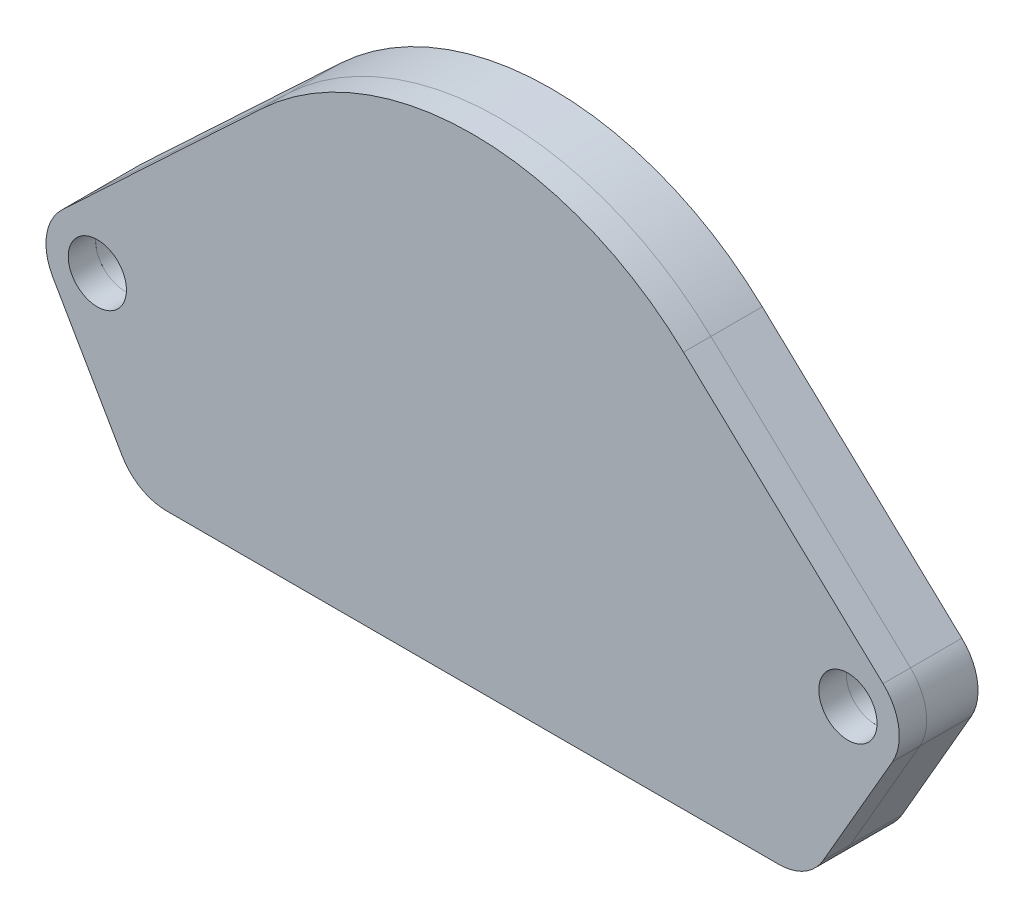
SolidWorks part; units mm, degrees
ref_plane "Front Plane" through (0, 0, 0) normal (0, 0, 1) x (1, 0, 0)
ref_plane "Top Plane" through (0, 0, 0) normal (0, 1, 0) x (1, 0, 0)
ref_plane "Right Plane" through (0, 0, 0) normal (1, 0, 0) x (0, 0, -1)
sketch "Sketch1" plane through (0, 0, 0) normal (0, 0, 1) x (1, 0, 0)
  line L0 (-12.3175, 13.1255) -> (-23.9729, 2.1876)
  line L1 (12.3175, 13.1255) -> (23.9729, 2.1876)
  line L2 (-21.92, 0) -> (21.92, 0) construction
  line L3 (-24.5181, -1.5) -> (-19.6106, -10)
  line L4 (-19.6106, -10) -> (19.6106, -10)
  line L5 (0, -10) -> (0, 0) construction
  line L6 (24.5181, -1.5) -> (19.6106, -10)
  arc A1 (-23.9729, 2.1876) -> (-24.5181, -1.5) centre (-21.92, 0) ccw
  arc A2 (24.5181, -1.5) -> (23.9729, 2.1876) centre (21.92, 0) ccw
  circle A3 centre (-21.92, 0) radius 1.7
  circle A4 centre (21.92, 0) radius 1.7
  arc A5 (12.3175, 13.1255) -> (-12.3175, 13.1255) centre (0, 0) ccw
  point P1 (0, 0)
  point P13 (-21.269, -9.3097)
  point P16 (0, 0)
  point P18 (-24.3403, -1.7726)
  point P19 (-17.123, -9.273)
  dimension "D1" = 43.84
  dimension "D2" = 18
  dimension "D3" = 6
  dimension "D5" = 3.4
  dimension "D4" = 10
  dimension "D6" = 60
extrude "Boss-Extrude1" add sketch "Sketch1" along normal blind 1.6
fillet "Fillet3" radius 3 2 edges at (19.6106, -10, 0.8) (-19.6106, -10, 0.8)
sketch "Sketch2" plane through (0, 0, 0) normal (0, 0, -1) x (-1, 0, 0)
  line L7 (-17.72, 0) -> (-17.72, -8)
  line L8 (17.72, 0) -> (17.72, -8)
  line L9 (-16.2662, 6.6772) -> (-10, 0) construction
  line L10 (-10, 0) -> (-10, -8) construction
  line L11 (-17.3599, 5.6507) -> (-11.5, -0.5936)
  line L12 (-11.5, -0.5936) -> (-11.5, -8)
  line L13 (-15.1724, 7.7036) -> (-8.5, 0.5936)
  line L15 (-17.8785, -8) -> (17.8785, -8)
  line L17 (18.7446, -7.5) -> (22.786, -0.5)
  line L18 (22.6043, 0.7292) -> (10.9489, 11.6671)
  line L19 (-10.9489, 11.6671) -> (-22.6043, 0.7292)
  line L20 (-22.786, -0.5) -> (-18.7446, -7.5)
  line L22 (-17.8785, -8) -> (17.8785, -8)
  line L24 (18.7446, -7.5) -> (22.786, -0.5)
  line L25 (22.6043, 0.7292) -> (10.9489, 11.6671)
  line L26 (-10.9489, 11.6671) -> (-22.6043, 0.7292)
  line L29 (-17.8785, -10) -> (17.8785, -10)
  line L31 (20.4766, -8.5) -> (24.5181, -1.5)
  line L32 (23.9729, 2.1876) -> (12.3175, 13.1255)
  line L33 (-12.3175, 13.1255) -> (-23.9729, 2.1876)
  line L34 (-24.5181, -1.5) -> (-20.4766, -8.5)
  line L36 (-17.8785, -10) -> (17.8785, -10)
  line L38 (20.4766, -8.5) -> (24.5181, -1.5)
  line L39 (23.9729, 2.1876) -> (12.3175, 13.1255)
  line L40 (-12.3175, 13.1255) -> (-23.9729, 2.1876)
  line L42 (-8.5, 0.5936) -> (-8.5, -8)
  line L43 (0, 0) -> (0, -8) construction
  line L44 (8.5, 0.5936) -> (8.5, -8)
  line L45 (10, 0) -> (10, -8) construction
  line L46 (11.5, -0.5936) -> (11.5, -8)
  line L47 (17.3599, 5.6507) -> (11.5, -0.5936)
  line L48 (16.2662, 6.6772) -> (10, 0) construction
  line L49 (15.1724, 7.7036) -> (8.5, 0.5936)
  line L51 (-22.786, -0.5) -> (-18.7446, -7.5)
  line L53 (-24.5181, -1.5) -> (-20.4766, -8.5)
  arc A14 (22.786, -0.5) -> (22.6043, 0.7292) centre (21.92, 0) ccw
  arc A15 (10.9489, 11.6671) -> (-10.9489, 11.6671) centre (0, 0) ccw
  arc A16 (-22.6043, 0.7292) -> (-22.786, -0.5) centre (-21.92, 0) ccw
  arc A17 (22.786, -0.5) -> (22.6043, 0.7292) centre (21.92, 0) ccw
  arc A18 (10.9489, 11.6671) -> (-10.9489, 11.6671) centre (0, 0) ccw
  circle A20 centre (-21.92, 0) radius 4.2
  circle A21 centre (-21.92, 0) radius 4.2
  circle A23 centre (21.92, 0) radius 4.2
  circle A24 centre (21.92, 0) radius 4.2
  arc A27 (-22.6043, 0.7292) -> (-22.786, -0.5) centre (-21.92, 0) ccw
  arc A31 (-18.7446, -7.5) -> (-17.8785, -8) centre (-17.8785, -7) ccw
  arc A33 (-18.7446, -7.5) -> (-17.8785, -8) centre (-17.8785, -7) ccw
  arc A34 (24.5181, -1.5) -> (23.9729, 2.1876) centre (21.92, 0) ccw
  arc A35 (12.3175, 13.1255) -> (-12.3175, 13.1255) centre (0, 0) ccw
  arc A36 (-23.9729, 2.1876) -> (-24.5181, -1.5) centre (-21.92, 0) ccw
  arc A41 (24.5181, -1.5) -> (23.9729, 2.1876) centre (21.92, 0) ccw
  arc A42 (12.3175, 13.1255) -> (-12.3175, 13.1255) centre (0, 0) ccw
  arc A43 (-23.9729, 2.1876) -> (-24.5181, -1.5) centre (-21.92, 0) ccw
  arc A45 (17.8785, -8) -> (18.7446, -7.5) centre (17.8785, -7) ccw
  arc A49 (17.8785, -8) -> (18.7446, -7.5) centre (17.8785, -7) ccw
  arc A53 (-20.4766, -8.5) -> (-17.8785, -10) centre (-17.8785, -7) ccw
  arc A55 (-20.4766, -8.5) -> (-17.8785, -10) centre (-17.8785, -7) ccw
  arc A56 (17.8785, -10) -> (20.4766, -8.5) centre (17.8785, -7) ccw
  arc A57 (17.8785, -10) -> (20.4766, -8.5) centre (17.8785, -7) ccw
  line M29 (-17.8785, -10) -> (17.8785, -10)
  line M33 (20.4766, -8.5) -> (24.5181, -1.5)
  arc M34 (24.5181, -1.5) -> (23.9729, 2.1876) centre (21.92, 0) ccw
  line M35 (23.9729, 2.1876) -> (12.3175, 13.1255)
  arc M36 (12.3175, 13.1255) -> (-12.3175, 13.1255) centre (0, 0) ccw
  line M37 (-12.3175, 13.1255) -> (-23.9729, 2.1876)
  arc M38 (-23.9729, 2.1876) -> (-24.5181, -1.5) centre (-21.92, 0) ccw
  line M39 (-24.5181, -1.5) -> (-20.4766, -8.5)
  circle M41 centre (21.92, 0) radius 1.7
  circle M42 centre (-21.92, 0) radius 1.7
  dimension "D5" = 1.5
  dimension "D7" = 10
  dimension "D1" = 2
  dimension "D2" = 2.5
  dimension "D3" = 2.5
  dimension "D4" = 0
  dimension "D6" = 1.5
extrude "Boss-Extrude2" add sketch "Sketch2" along normal blind 3 separate body contours A24 L39 A21 L26 A18 L25 M36 M37 | L26 A21 L40 L51 M38 M39 M42 | A24 L22 A21 L53 M29 M33 | A21 L26 L51 M42 | L25 A24 L24 M41 | A24 L25 L24 L38 M35 M41 M34 | A21 L22 L7 | A24 L8 L22 | L25 L49 L44 L22 L46 L47 | L42 L13 L26 L11 L12 L22 region at (19.595, -0.3437, 0) region at (18.7009, -4.8445, 0) region at (0, -8.4508, 0) region at (20.5467, 4.453, 0) region at (20.6837, 2.6677, 0) region at (11.6399, -0.0705, 0) region at (-11.6399, -0.0705, 0) region at (-22.8333, 3.1209, 0) region at (-18.7009, -4.8445, 0) region at (-19.595, -0.3437, 0)
sketch "Sketch3" plane through (0, 0, 0) normal (0, 0, 1) x (1, 0, 0)
  line L0 (0, 0) -> (0, 18) construction
  circle A0 centre (-6.85, 13.3) radius 2
  arc A1 (12.3175, 13.1255) -> (-12.3175, 13.1255) centre (0, 0) ccw construction
  circle A2 centre (6.85, 13.3) radius 2
  point P10 (-8.2517, 13.3)
  point P11 (0, 0)
  dimension "D1" = 13.3
  dimension "D3" = 4
  dimension "D2" = 13.7
extrude "Cut-Extrude1" cut sketch "Sketch3" against normal through all draft 20
fillet "Fillet2" radius 1.5 18 edges at (19.6298, 3.5206, -1.5) (-19.6298, 3.5206, -1.5) (-8.5, -8, -1.5) (-8.5, 0.5936, -1.5) (-15.1724, 7.7036, -1.5) (15.1724, 7.7036, -1.5) (8.5, 0.5936, -1.5) (8.5, -8, -1.5) (-17.3599, 5.6507, -1.5) (-11.5, -0.5936, -1.5) (-11.5, -8, -1.5) (-17.72, -8, -1.5) (17.72, -8, -1.5) (11.5, -8, -1.5) (11.5, -0.5936, -1.5) (17.3599, 5.6507, -1.5) (7.2168, 14.28, -2.6201) (-7.4348, 14.1677, -2.6201)
